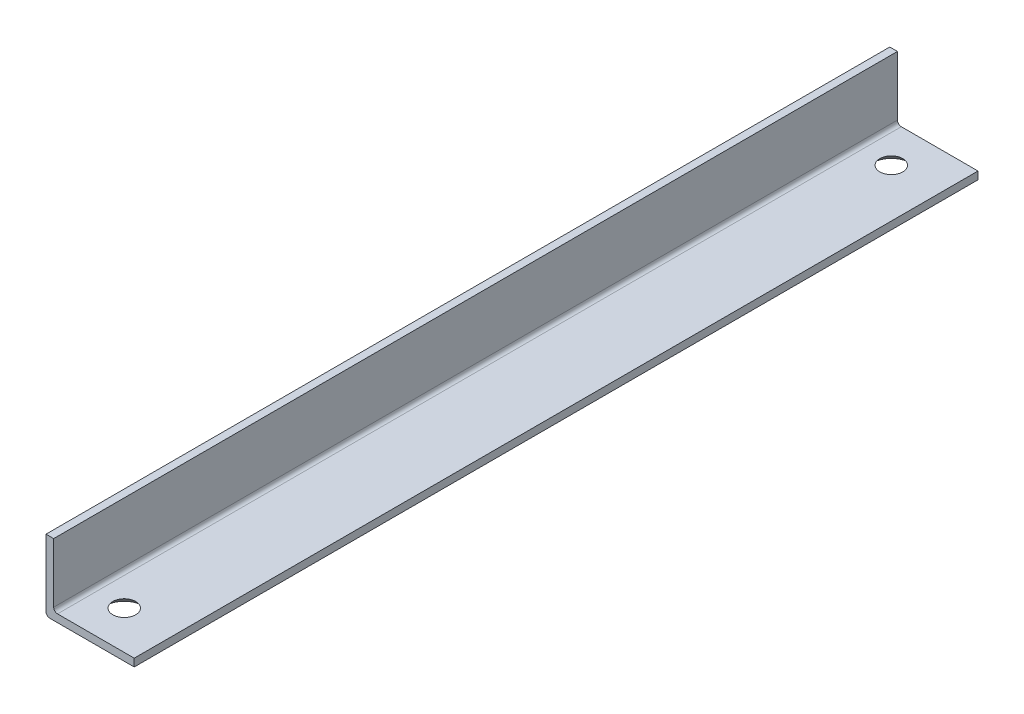
SolidWorks part; units mm, degrees
ref_plane "Plan de face" through (0, 0, 0) normal (0, 0, 1) x (1, 0, 0)
ref_plane "Plan de dessus" through (0, 0, 0) normal (0, 1, 0) x (1, 0, 0)
ref_plane "Plan de droite" through (0, 0, 0) normal (1, 0, 0) x (0, 0, -1)
sketch "Esquisse1" plane through (0, 0, 0) normal (0, 0, 1) x (1, 0, 0)
  line L0 (0, 0.5) -> (0, 9.25)
  line L1 (0, 9.25) -> (1, 9.25)
  line L2 (1, 9.25) -> (1, 1.5)
  line L3 (1.5, 1) -> (11.5, 1)
  line L4 (11.5, 1) -> (11.5, 0)
  line L5 (11.5, 0) -> (0.5, 0)
  arc A0 (1, 1.5) -> (1.5, 1) centre (1.5, 1.5) ccw
  arc A1 (0.5, 0) -> (0, 0.5) centre (0.5, 0.5) cw
  point P11 (0, 0)
  dimension "D5" = 0.5
  dimension "D1" = 9.25
  dimension "D2" = 11.5
  dimension "D3" = 1
  dimension "D4" = 1
extrude "Boss.-Extru.1" add sketch "Esquisse1" along normal blind 110
sketch "Esquisse2" plane through (0, 0, 0) normal (0, -1, 0) x (1, 0, 0)
  line L0 (0.5, 0) -> (11.5, 0) construction
  line L1 (0.5, 110) -> (11.5, 110) construction
  line L4 (0, 110) -> (0, 0) construction
  circle A0 centre (5.2, 5) radius 1.5
  circle A1 centre (5.2, 105) radius 1.5
  dimension "D3" = 3
  dimension "D4" = 3
  dimension "D1" = 5
  dimension "D2" = 5
  dimension "D5" = 5.2
  dimension "D6" = 5.2
extrude "Enlèv. mat.-Extru.1" cut sketch "Esquisse2" against normal blind 5
chamfer "Chanfrein1" distance 1 angle 45 2 edges at (6.7, 0, 105) (6.7, 0, 5)
